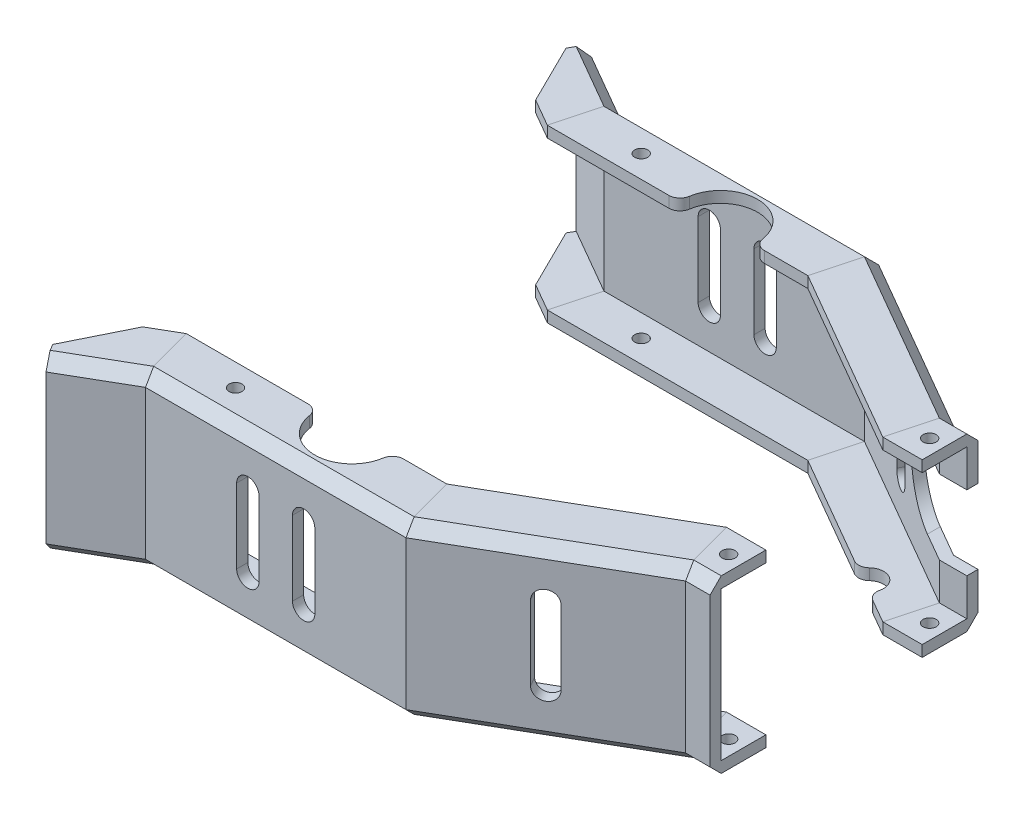
SolidWorks part; units mm, degrees
material "ABS PC"
ref_plane "Front Plane" through (0, 0, 0) normal (0, 0, 1) x (1, 0, 0)
ref_plane "Top Plane" through (0, 0, 0) normal (0, 1, 0) x (1, 0, 0)
ref_plane "Right Plane" through (0, 0, 0) normal (1, 0, 0) x (0, 0, -1)
sketch "Sketch6" plane through (0, 0, 0) normal (0, 1, 0) x (1, 0, 0)
  line L0 (0, 0) -> (-70, 0)
  line L1 (-70, 0) -> (-87.3205, -10)
  line L2 (0, 0) -> (47.6314, 27.5)
  line L3 (47.6314, 27.5) -> (54.6314, 27.5)
  dimension "D1" = 70
  dimension "D2" = 20
  dimension "D3" = 150
  dimension "D4" = 55
  dimension "D5" = 7
ref_plane "Plane5" through (0, 0, 0) normal (1, 0, 0) x (0, 0, -1)
sketch "Sketch7" plane through (0, 0, 0) normal (1, 0, 0) x (0, 0, -1)
  line L0 (1.3953, 0) -> (11.0315, 0) construction
  line L2 (-1.6047, -23) -> (-1.6047, 23)
  line L4 (1.3953, -20) -> (1.3953, 20)
  line L5 (-1.6047, -23) -> (1.3953, 20) construction
  line L6 (-1.6047, 23) -> (1.3953, -20) construction
  line L7 (13.3953, 20) -> (13.3953, 23)
  line L8 (1.3953, -20) -> (13.3953, -20)
  line L10 (-1.6047, -23) -> (13.3953, -23)
  line L11 (13.3953, -20) -> (13.3953, -23)
  line L12 (-1.6047, 23) -> (13.3953, 23)
  line L14 (1.3953, 20) -> (13.3953, 20)
  point P0 (0, 0)
  dimension "D1" = 3
  dimension "D3" = 3
  dimension "D2" = 40
  dimension "D5" = 15
sweep "Sweep8" add profiles "Sketch7" path "Sketch6"
ref_plane "Plane6" through (0, 0, -61.8953) normal (0, 0, -1) x (-1, 0, 0)
sketch "Sketch8" plane through (0, 23, 0) normal (0, 1, 0) x (1, 0, 0)
  line L1 (-73.5893, 13.3953) -> (-94.0182, 1.6007) construction
  line L3 (-89.0182, -7.0595) -> (-94.0182, 1.6007)
  line L4 (-94.0182, 1.6007) -> (-81.0278, 9.1007)
  line L5 (-94.0182, 1.6007) -> (-86.5182, -11.3897) construction
  line L6 (-81.0278, 9.1007) -> (-89.0182, -7.0595)
  dimension "D1" = 15
  dimension "D2" = 10
extrude "Cut-Extrude1" cut sketch "Sketch8" against normal through all
sketch "Sketch10" plane through (0, 23, 0) normal (0, 1, 0) x (1, 0, 0)
  line L0 (-3.5893, 13.3953) -> (-73.5893, 13.3953) construction
  line L1 (-38.0893, 13.3953) -> (-18.0893, 13.3953)
  line L2 (-38.0893, 13.3953) -> (-38.0893, 12.3953)
  line L3 (-38.0893, 12.3953) -> (-18.0893, 12.3953) construction
  line L4 (-18.0893, 13.3953) -> (-18.0893, 12.3953)
  arc A0 (-38.0893, 12.3953) -> (-18.0893, 12.3953) centre (-28.0893, 12.3953) ccw
  dimension "D1" = 1
  dimension "D2" = 20
  dimension "D3" = 24.5
extrude "Cut-Extrude3" cut sketch "Sketch10" against normal blind 5
sketch "Sketch11" plane through (0, 0, 1.6047) normal (0, 0, 1) x (1, 0, 0)
  line L0 (-34.57, 23) -> (-34.57, -23) construction
  line L3 (-42.07, -10) -> (-42.07, 10) construction
  line L4 (-45.07, -10) -> (-45.07, 10)
  line L5 (-39.07, -10) -> (-39.07, 10)
  line L6 (-27.07, -10) -> (-27.07, 10) construction
  line L7 (-24.07, -10) -> (-24.07, 10)
  line L8 (-30.07, -10) -> (-30.07, 10)
  line L9 (-34.57, 0) -> (-42.07, 0) construction
  line L10 (0.43, 23) -> (-69.57, 23) construction
  line L11 (0.43, -23) -> (-69.57, -23) construction
  arc A0 (-45.07, -10) -> (-39.07, -10) centre (-42.07, -10) ccw
  arc A1 (-39.07, 10) -> (-45.07, 10) centre (-42.07, 10) ccw
  arc A2 (-24.07, -10) -> (-30.07, -10) centre (-27.07, -10) cw
  arc A3 (-30.07, 10) -> (-24.07, 10) centre (-27.07, 10) cw
  point P8 (-42.07, 0)
  point P15 (-27.07, 0)
  dimension "D1" = 15
  dimension "D2" = 6
  dimension "D3" = 20
extrude "Cut-Extrude4" cut sketch "Sketch11" against normal blind 10
chamfer "Chamfer1" distance 3 angle 45 8 edges at (-78.0441, -23, 6.4972) (-34.57, -23, 1.6047) (24.2457, -23, -12.1453) (-78.0441, 23, 6.4972) (-34.57, 23, 1.6047) (24.2457, 23, -12.1453) (51.3464, -23, -25.8953) (51.3464, 23, -25.8953)
sketch "Sketch14" plane through (0.8023, 0, 1.3897) normal (0.5, 0, 0.866) x (0.866, 0, -0.5)
  line L0 (27.07, -10) -> (27.07, 10) construction
  line L1 (24.07, -10) -> (24.07, 10)
  line L2 (30.07, -10) -> (30.07, 10)
  line L3 (27.07, -20) -> (27.07, -10) construction
  line L5 (0, 0) -> (27.07, 0) construction
  line L6 (-0.43, -20) -> (54.57, -20) construction
  arc A0 (24.07, -10) -> (30.07, -10) centre (27.07, -10) ccw
  arc A1 (30.07, 10) -> (24.07, 10) centre (27.07, 10) ccw
  point P2 (27.07, 0)
  dimension "D1" = 20
  dimension "D2" = 6
extrude "Cut-Extrude6" cut sketch "Sketch14" against normal blind 3
hole_wizard "Ø3.5 (3.5) Diameter Hole1" positions "Sketch18" profile "Sketch19" hole size "Ø3.5" standard "ANSI Metric" end condition through all
sketch "Sketch18" plane through (0, -23, 0) normal (0, -1, 0) x (-1, 0, 0)
  line L6 (-50.6314, 34.8953) -> (-50.6314, 28.8953) construction
  line L7 (-54.6314, 28.8953) -> (-47.2575, 28.8953) construction
  line L11 (54.3686, 7.3953) -> (54.3686, 1.3953) construction
  line L12 (0.3739, 1.3953) -> (70.3739, 1.3953) construction
  line L14 (-54.6314, 28.8953) -> (-54.6314, 40.8953) construction
  point P0 (54.3686, 7.3953)
  point P2 (-50.6314, 34.8953)
  dimension "D1" = 6
  dimension "D2" = 105
  dimension "D3" = 4
sketch "Sketch19" plane through (-54.3686, -23, -7.3953) normal (1, 0, 0) x (0, 0, -1)
  line L0 (0, 0) -> (0, 46)
  line L1 (0, 46) -> (1.75, 46)
  line L2 (1.75, 46) -> (1.75, 0)
  line L5 (1.75, 0) -> (0, 0)
  line L11 (0, -6.35) -> (0, 107.95) construction
  dimension "Thru Hole Dia." = 3.5
  dimension "Thru Hole Depth" = 46
sketch "Sketch22" plane through (0, -23, 0) normal (0, -1, 0) x (1, 0, 0)
  line L0 (28.4537, -31.8953) -> (35.3819, -35.8953)
  line L1 (28.4537, -31.8953) -> (28.9537, -31.0293)
  line L2 (35.3819, -35.8953) -> (35.8819, -35.0293)
  line L3 (28.9537, -31.0293) -> (35.8819, -35.0293)
  line L4 (44.0421, -40.8953) -> (-3.5893, -13.3953) construction
  arc A0 (28.9537, -31.0293) -> (35.8819, -35.0293) centre (32.4178, -33.0293) cw
  point P6 (31.9178, -33.8953)
  line M7 (-3.5893, -13.3953) -> (44.0421, -40.8953)
  dimension "D1" = 1
  dimension "D2" = 8
  dimension "D3" = 14
extrude "Cut-Extrude9" cut sketch "Sketch22" against normal blind 10 contours A0 L3 | L3 L1 L2 M7 region at (32.1678, -23, -33.4623) region at (33.2666, -23, -31.5591)
mirror "Mirror2" about plane through (0, 0, -61.8953) normal (0, 0, -1) of bodies 116 103
sketch "Sketch20" plane through (0, 0, -97.8953) normal (0, 0, -1) x (-1, 0, 0)
  line L0 (-54.6314, 0) -> (-47.1314, 0) construction
  line L1 (-54.6314, 20) -> (-54.6314, -20) construction
  line L3 (-39.6314, -10) -> (-54.6314, -10)
  line L4 (-39.6314, -10) -> (-39.6314, 10)
  line L5 (-39.6314, 10) -> (-54.6314, 10)
  line L6 (-54.6314, -10) -> (-54.6314, 10)
  line L7 (-39.6314, -10) -> (-54.6314, 10) construction
  line L8 (-39.6314, 10) -> (-54.6314, -10) construction
  arc A0 (-39.6314, 10) -> (-39.6314, -10) centre (-39.6314, 0) cw
  point P5 (-47.1314, 0)
  line M3 (-48.0614, -20) -> (-48.0614, 20)
  line M5 (-54.6314, 20) -> (-54.6314, -20)
  dimension "D1" = 20
  dimension "D2" = 15
extrude "Cut-Extrude7" cut sketch "Sketch20" against normal blind 5 and the other way through all contours A0 L4 | L5 L3 M3 M5 | L4 L5 L3 M3 region at (43.8464, 0, -97.8953) region at (35.3873, 0, -97.8953) region at (51.3464, 0, -97.8953)
sketch "Sketch21" plane through (0, 0, -25.8953) normal (0, 0, 1) x (1, 0, 0)
  line L0 (54.6314, 0) -> (49.6314, 0) construction
  line L2 (54.6314, 20) -> (54.6314, -20) construction
  line L3 (54.6314, -7.5) -> (44.6314, -7.5)
  line L4 (54.6314, -7.5) -> (54.6314, 7.5)
  line L5 (54.6314, 7.5) -> (44.6314, 7.5)
  line L6 (44.6314, -7.5) -> (44.6314, 7.5)
  line L7 (54.6314, -7.5) -> (44.6314, 7.5) construction
  line L8 (54.6314, 7.5) -> (44.6314, -7.5) construction
  arc A0 (44.6314, 7.5) -> (44.6314, -7.5) centre (44.6314, 0) ccw
  point P5 (49.6314, 0)
  line M14 (48.0614, 20) -> (48.0614, -20)
  line M16 (54.6314, -20) -> (54.6314, 20)
  dimension "D1" = 15
  dimension "D2" = 10
extrude "Cut-Extrude8" [suppressed] cut sketch "Sketch21" against normal blind 10 and the other way blind 10 contours A0 M14 | L6 A0 M14 | L6 L3 L5 M16
fillet "Fillet1" radius 3 4 edges at (28.4537, -21.5, -31.8953) (35.3819, -21.5, -35.8953) (-18.0893, 21.5, -13.3953) (-38.0893, 21.5, -13.3953)
fillet "Fillet2" radius 3 4 edges at (-38.0893, 21.5, -110.3953) (-18.0893, 21.5, -110.3953) (28.4537, -21.5, -91.8953) (35.3819, -21.5, -87.8953)
